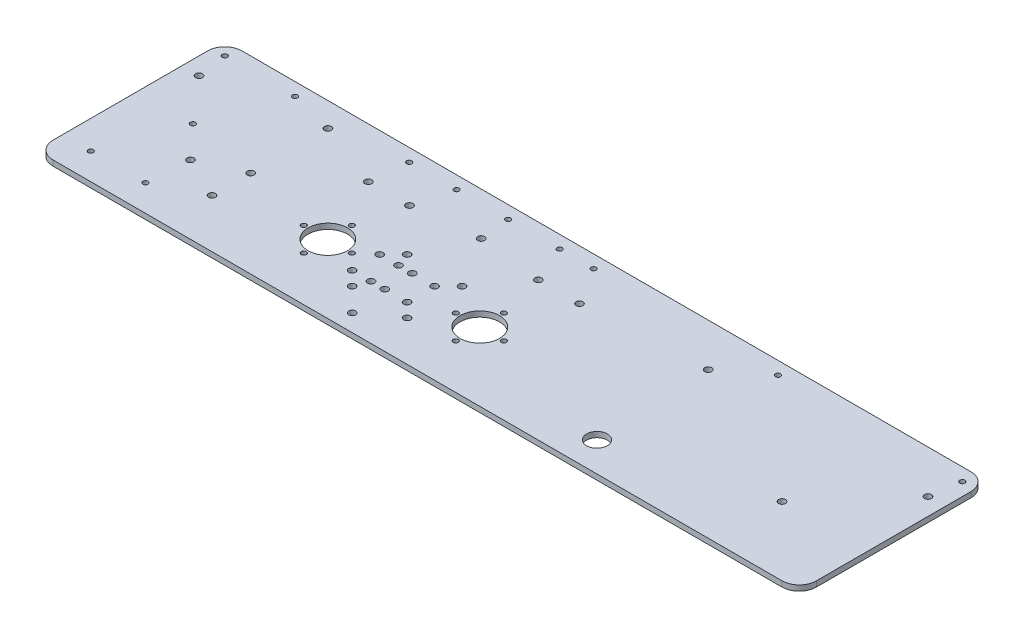
SolidWorks part; units mm, degrees
ref_plane "Front" through (0, 0, 0) normal (0, 0, 1) x (1, 0, 0)
ref_plane "Top" through (0, 0, 0) normal (0, 1, 0) x (1, 0, 0)
ref_plane "Right" through (0, 0, 0) normal (1, 0, 0) x (0, 0, -1)
sketch "Sketch1" plane through (0, 0, 0) normal (0, 1, 0) x (1, 0, 0)
  line L0 (-26.7996, 0) -> (-26.7996, 40)
  line L1 (-26.7996, 0) -> (417.7004, 0)
  line L2 (-26.7996, 0) -> (-26.7996, 110)
  line L3 (-26.7996, 110) -> (417.7004, 110)
  line L4 (417.7004, 0) -> (417.7004, 110)
  line L5 (-26.7996, 40) -> (23.2004, 40)
  line L6 (417.7004, 0) -> (417.7004, 40)
  line L7 (417.7004, 40) -> (367.7004, 40)
  line L8 (23.2004, 40) -> (103.2004, 40)
  line L9 (367.7004, 40) -> (191.7004, 40)
  line L10 (-26.7996, 110) -> (-26.7996, 85)
  line L11 (-26.7996, 85) -> (417.7004, 85)
  line L12 (-26.7996, 85) -> (-16.7996, 85)
  line L13 (417.7004, 85) -> (407.7004, 85)
  line L14 (103.2004, 40) -> (191.7004, 40)
  line L15 (147.4504, 40) -> (147.4504, 85)
  line L16 (279.7004, 40) -> (279.7004, 85)
  line L17 (147.4504, 40) -> (147.4504, 10)
  line L18 (-26.7996, 110) -> (-26.7996, 102.5)
  line L19 (-26.7996, 102.5) -> (417.7004, 102.5)
  line L20 (-26.7996, 102.5) -> (-19.2996, 102.5)
  line L21 (417.7004, 102.5) -> (410.2004, 102.5)
  line L22 (195.4504, 102.5) -> (410.2004, 102.5)
  line L23 (-19.2996, 102.5) -> (195.4504, 102.5)
  line L24 (417.7004, 0) -> (417.7004, 17.2282)
  line L25 (417.7004, 17.2282) -> (282.7004, 17.2282)
  circle A10 centre (367.7004, 40) radius 2
  circle A11 centre (23.2004, 40) radius 2
  circle A12 centre (103.2004, 40) radius 11.5
  circle A13 centre (103.2004, 40) radius 14
  circle A15 centre (103.2004, 54) radius 1.5
  circle A16 centre (89.2004, 40) radius 1.5
  circle A17 centre (103.2004, 26) radius 1.5
  circle A18 centre (117.2004, 40) radius 1.5
  circle A19 centre (191.7004, 40) radius 11.5
  circle A20 centre (191.7004, 40) radius 14
  circle A21 centre (191.7004, 26) radius 1.5
  circle A22 centre (205.7004, 40) radius 1.5
  circle A23 centre (191.7004, 54) radius 1.5
  circle A24 centre (177.7004, 40) radius 1.5
  circle A25 centre (-16.7996, 85) radius 2
  circle A26 centre (407.7004, 85) radius 2
  circle A27 centre (147.4504, 85) radius 2
  circle A28 centre (279.7004, 85) radius 2
  circle A29 centre (147.4504, 10) radius 2
  circle A30 centre (195.4504, 102.5) radius 1.5
  circle A31 centre (-19.2996, 102.5) radius 1.5
  circle A32 centre (410.2004, 102.5) radius 1.5
  circle A33 centre (302.8254, 102.5) radius 1.5
  circle A34 centre (88.0754, 102.5) radius 1.5
  circle A35 centre (282.7004, 17.2282) radius 6
  dimension "D3" = 40
  dimension "D7" = 80
  dimension "D8" = 176
  dimension "D9" = 25
  dimension "D11" = 10
  dimension "D12" = 30
  dimension "D13" = 7.5
  dimension "D14" = 7.5
  dimension "D16" = 17.2282
  dimension "D1" = 110
  dimension "D2" = 444.5
  dimension "D4" = 50
  dimension "D5" = 40
  dimension "D6" = 50
  dimension "D10" = 10
  dimension "D15" = 7.5
  dimension "D17" = 135
extrude "Boss-Extrude1" add sketch "Sketch1" along normal blind 3.175 contours A18 L14 A12 L8 A16 A13 A17 | A18 A13 A15 A16 L8 A12 L14 | A24 L14 A19 L9 A22 A20 A23 | A24 A20 A21 A22 L9 A19 L14 | A29 L14 A18 A13 A17 A16 L8 A11 L5 L0 L1 L4 L7 A10 L9 A22 A20 A21 A24 | A28 L11 A27 L15 L14 A24 A20 A23 A22 L9 L16 | A27 L11 A25 L2 L5 A11 L8 A16 A13 A15 A18 L14 L15 | A28 L11 A26 L13 L4 L3 L2 A25 A27 | A28 L16 L9 A10 L7 L4 L13 A26 L11 | A34 L23 A30 L22 A33 A32 L21 L4 L3 L10 L19 A31 region at (196.684, 0, -19.4923) region at (58.5861, 0, -63.184) region at (195.421, 0, -93.7571) region at (195.4504, 0, -106.2666) region at (348.6559, 0, -62.489) region at (93.521, 0, -49.6794) region at (90.515, 0, -38.754) region at (214.7998, 0, -63.4004) region at (204.3858, 0, -41.246) region at (201.3798, 0, -30.3206)
fillet "Fillet1" radius 10 4 edges at (417.7004, 1.5875, -110) (417.7004, 1.5875, 0) (-26.7996, 1.5875, 0) (-26.7996, 1.5875, -110)
sketch "Sketch2" plane through (0, 3.175, 0) normal (0, 1, 0) x (1, 0, 0)
  line L0 (-26.7996, 55.4056) -> (36.2004, 55.4056)
  line L1 (-26.7996, 10) -> (-26.7996, 100) construction
  line L2 (36.2004, 55.4056) -> (76.2004, 55.4056)
  line L3 (-16.7996, 110) -> (407.7004, 110) construction
  line L4 (36.2004, 55.4056) -> (36.2004, 23.4056)
  line L5 (36.2004, 23.4056) -> (68.2004, 23.4056)
  line L6 (76.2004, 55.4056) -> (165.9504, 55.4056)
  line L7 (165.9504, 55.4056) -> (133.9504, 55.4056)
  line L8 (133.9504, 55.4056) -> (133.9504, 23.4056)
  line L9 (133.9504, 23.4056) -> (165.9504, 23.4056)
  line L10 (133.9504, 23.4056) -> (125.9504, 23.4056)
  line L11 (125.9504, 23.4056) -> (125.9504, 55.4056)
  line L12 (165.9504, 55.4056) -> (157.9504, 55.4056)
  line L13 (157.9504, 55.4056) -> (157.9504, 23.4056)
  line L14 (157.9504, 23.4056) -> (157.9504, 31.4056)
  line L15 (157.9504, 55.4056) -> (157.9504, 47.4056)
  line L16 (157.9504, 47.4056) -> (133.9504, 47.4056)
  circle A4 centre (133.9504, 55.4056) radius 2
  circle A5 centre (165.9504, 55.4056) radius 2
  circle A9 centre (133.9504, 23.4056) radius 2
  circle A10 centre (165.9504, 23.4056) radius 2
  circle A11 centre (157.9504, 31.4056) radius 2
  circle A12 centre (125.9504, 31.4056) radius 2
  circle A13 centre (125.9504, 47.4056) radius 2
  circle A14 centre (157.9504, 47.4056) radius 2
  dimension "D5" = 89.75
  dimension "D6" = 32
  dimension "D7" = 8
  dimension "D10" = 8
  dimension "D1" = 63
  dimension "D2" = 40
  dimension "D3" = 54.5944
  dimension "D4" = 32
  dimension "D8" = 8
  dimension "D9" = 8
extrude "Cut-Extrude1" cut sketch "Sketch2" against normal blind 10 contours A4 | A5 | A13 | A12 | A9 | A10 | A11 | A14
sketch "Sketch3" plane through (0, 0, 0) normal (0, -1, 0) x (1, 0, 0)
  line L0 (133.9504, -55.4056) -> (133.9504, -47.4056)
  line L1 (133.9504, -47.4056) -> (136.9504, -47.4056)
  line L2 (136.9504, -47.4056) -> (144.9504, -47.4056)
  line L3 (136.9504, -47.4056) -> (136.9504, -31.4056)
  line L4 (136.9504, -31.4056) -> (144.9504, -31.4056)
  circle A0 centre (144.9504, -47.4056) radius 2
  circle A1 centre (136.9504, -47.4056) radius 2
  circle A2 centre (144.9504, -31.4056) radius 2
  circle A3 centre (136.9504, -31.4056) radius 2
  dimension "D3" = 8
  dimension "D1" = 3
  dimension "D2" = 8
  dimension "D4" = 16
extrude "Cut-Extrude2" cut sketch "Sketch3" against normal blind 10 contours L2 A1 L1 | L1 A1 L2 | A2 | L4 A3 L3 | L3 A1 L1 | L3 A3 L4 | A0 region at (136.1016, 0, -46.5568) region at (144.9504, 0, -29.4622) region at (136.6675, 0, -31.1227) region at (137.7992, 0, -32.2544) region at (136.9504, 0, -48.2544) region at (137.7992, 0, -46.5568)
sketch "Sketch4" plane through (0, 3.175, 0) normal (0, 1, 0) x (1, 0, 0)
  circle A0 centre (21.5907, 102.5) radius 1.5
  circle A1 centre (5.6648, 58.9528) radius 1.5
  circle A2 centre (-10.261, 15.4056) radius 1.5
  circle A3 centre (47.3504, 50.9056) radius 2
  circle A4 centre (115.6708, 102.5) radius 1.5
  circle A5 centre (145.6708, 102.5) radius 1.5
  circle A6 centre (175.6708, 102.5) radius 1.5
  circle A7 centre (47.3504, 95.9056) radius 2
  circle A8 centre (21.5907, 15.4056) radius 1.5
  circle A9 centre (47.3504, 28.4056) radius 2
  circle A10 centre (208.9504, 80.8056) radius 2
  circle A11 centre (184.9504, 80.8056) radius 2
  circle A12 centre (109.9504, 80.8056) radius 2
  circle A13 centre (85.9504, 80.8056) radius 2
extrude "Cut-Extrude3" cut sketch "Sketch4" against normal blind 6.35
